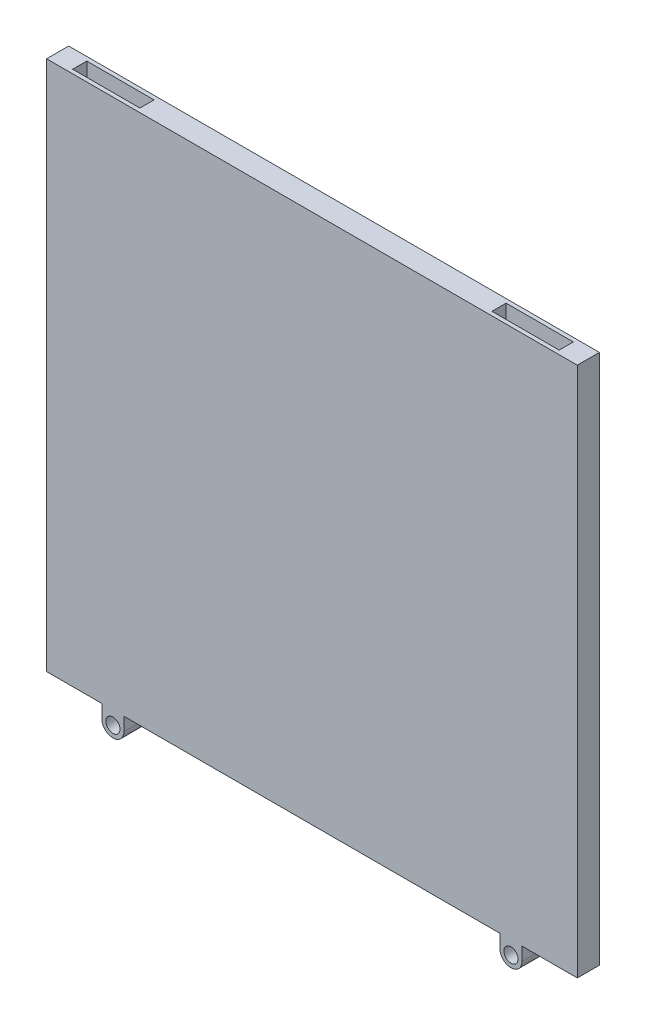
SolidWorks part; units mm, degrees
ref_plane "Front Plane" through (0, 0, 0) normal (0, 0, 1) x (1, 0, 0)
ref_plane "Top Plane" through (0, 0, 0) normal (0, 1, 0) x (1, 0, 0)
ref_plane "Right Plane" through (0, 0, 0) normal (1, 0, 0) x (0, 0, -1)
sketch "Sketch1" plane through (0, 0, 0) normal (0, 0, 1) x (1, 0, 0)
  line L1 (60, -60) -> (-60, -60)
  line L2 (60, -60) -> (60, 60)
  line L3 (60, 60) -> (-60, 60)
  line L4 (-60, -60) -> (-60, 60)
  line L5 (60, -60) -> (-60, 60) construction
  line L6 (60, 60) -> (-60, -60) construction
  point P0 (0, 0)
  dimension "D1" = 120
  dimension "D2" = 120
extrude "Boss-Extrude1" add sketch "Sketch1" along normal mid plane 5 contours L2 L3 L4 L1
sketch "Sketch4" plane through (0, 60, 0) normal (0, 1, 0) x (1, 0, 0)
  line L0 (-60, 0) -> (60, 0) construction
  line L1 (-55, -1.6) -> (-39.8, -1.6)
  line L2 (-55, -1.6) -> (-55, 1.6)
  line L3 (-55, 1.6) -> (-39.8, 1.6)
  line L4 (-39.8, -1.6) -> (-39.8, 1.6)
  line L5 (-55, -1.6) -> (-39.8, 1.6) construction
  line L6 (-55, 1.6) -> (-39.8, -1.6) construction
  line L7 (-60, -2.5) -> (-60, 2.5) construction
  line L8 (60, -2.5) -> (60, 2.5) construction
  line L9 (0, -2.75) -> (0, 2.75) construction
  line L10 (55, -1.6) -> (39.8, -1.6)
  line L11 (39.8, -1.6) -> (39.8, 1.6)
  line L12 (55, 1.6) -> (39.8, 1.6)
  line L13 (55, -1.6) -> (55, 1.6)
  point P0 (-47.4, 0)
  dimension "D1" = 15.2
  dimension "D2" = 3.2
  dimension "D3" = 5
extrude "Cut-Extrude1" cut sketch "Sketch4" against normal blind 20
sketch "Sketch6" plane through (0, 0, 2.5) normal (0, 0, 1) x (1, 0, 0)
  line L0 (60, -60) -> (-60, -60) construction
  line L1 (42.5, -60) -> (47.5, -60)
  line L2 (42.5, -60) -> (42.5, -63)
  line L4 (47.5, -60) -> (47.5, -63)
  line L5 (60, -60) -> (60, 60) construction
  arc A0 (42.5, -63) -> (47.5, -63) centre (45, -63) ccw
  circle A1 centre (45, -63) radius 1.6
  dimension "D2" = 3.2
  dimension "D4" = 3
  dimension "D1" = 5
  dimension "D3" = 15
extrude "Boss-Extrude2" add sketch "Sketch6" against normal up to surface (5 mm away) up to face at (0, 0, -2.5)
mirror "Mirror1" about plane through (0, 0, 0) normal (1, 0, 0) of "Boss-Extrude2"
